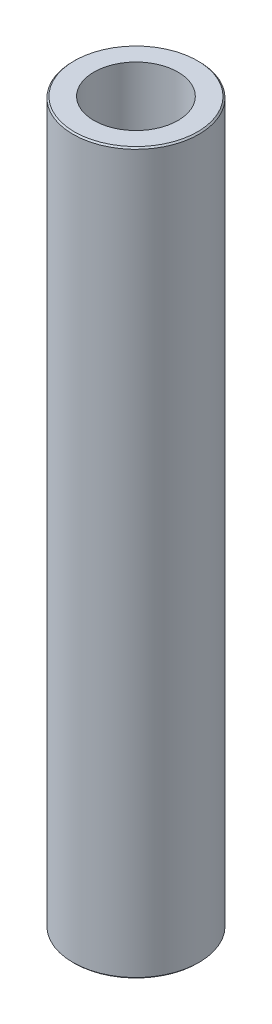
SolidWorks part; units mm, degrees
ref_plane "Front Plane" through (0, 0, 0) normal (0, 0, 1) x (1, 0, 0)
ref_plane "Top Plane" through (0, 0, 0) normal (0, 1, 0) x (1, 0, 0)
ref_plane "Right Plane" through (0, 0, 0) normal (1, 0, 0) x (0, 0, -1)
sketch "Sketch1" plane through (0, 0, 0) normal (0, 1, 0) x (1, 0, 0)
  circle A0 centre (0, 0) radius 52.5
  dimension "SHAFT_OD" = 105
extrude "Boss-Extrude1" add sketch "Sketch1" along normal blind 600
sketch "Sketch2" plane through (0, 0, 0) normal (0, 1, 0) x (1, 0, 0)
  circle A0 centre (0, 0) radius 35.0089
  dimension "BORE_D" = 70.0178
extrude "Cut-Extrude1" cut sketch "Sketch2" along normal through all
chamfer "Chamfer1" distance 1.1817 angle 45 2 edges at (0, 600, 52.5) (0, 0, 52.5)
